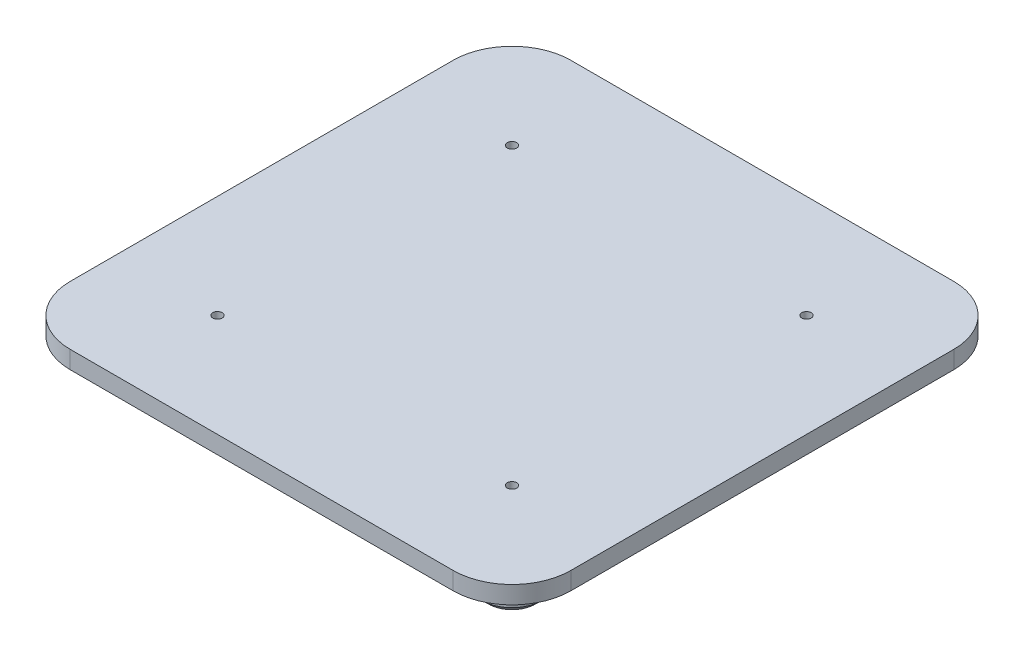
SolidWorks part; units mm, degrees
material "ABS"
ref_plane "前视基准面" through (0, 0, 0) normal (0, 0, 1) x (1, 0, 0)
ref_plane "上视基准面" through (0, 0, 0) normal (0, 1, 0) x (1, 0, 0)
ref_plane "右视基准面" through (0, 0, 0) normal (1, 0, 0) x (0, 0, -1)
sketch "草图1" plane through (0, 0, 0) normal (0, 1, 0) x (1, 0, 0)
  line L0 (-33.45, 33.45) -> (-33.45, -33.45)
  line L1 (-37.45, 37.45) -> (37.45, 37.45)
  line L2 (-37.45, 37.45) -> (-37.45, -37.45)
  line L3 (-37.45, -37.45) -> (37.45, -37.45)
  line L4 (37.45, 37.45) -> (37.45, -37.45)
  line L5 (-37.45, 37.45) -> (37.45, -37.45) construction
  line L6 (-37.45, -37.45) -> (37.45, 37.45) construction
  line L7 (-33.45, -33.45) -> (33.45, -33.45)
  line L8 (33.45, 33.45) -> (33.45, -33.45)
  line L9 (-33.45, 33.45) -> (33.45, 33.45)
  point P0 (0, 0)
  dimension "D1" = 74.9
  dimension "D3" = 74.9
  dimension "D2" = 4
extrude "凸台-拉伸1" add sketch "草图1" along normal blind 5
sketch "草图2" plane through (0, 5, 0) normal (0, 1, 0) x (1, 0, 0)
  line L1 (-42.5, -42.5) -> (42.5, -42.5)
  line L2 (-42.5, -42.5) -> (-42.5, 42.5)
  line L3 (-42.5, 42.5) -> (42.5, 42.5)
  line L4 (42.5, -42.5) -> (42.5, 42.5)
  line L5 (-42.5, -42.5) -> (42.5, 42.5) construction
  line L6 (-42.5, 42.5) -> (42.5, -42.5) construction
  point P0 (0, 0)
  dimension "D1" = 85
  dimension "D2" = 85
extrude "凸台-拉伸2" add sketch "草图2" along normal blind 3
fillet "圆角2" radius 5 4 edges at (-37.45, 2.5, 37.45) (-37.45, 2.5, -37.45) (37.45, 2.5, -37.45) (37.45, 2.5, 37.45)
sketch "草图3" plane through (0, 0, -37.45) normal (0, 0, -1) x (-1, 0, 0)
  line L0 (-32.45, 0) -> (32.45, 0) construction
  line L1 (22.0629, -5) -> (-22.0629, -5)
  line L2 (22.0629, -5) -> (22.0629, 5)
  line L3 (22.0629, 5) -> (-22.0629, 5)
  line L4 (-22.0629, -5) -> (-22.0629, 5)
  line L5 (22.0629, -5) -> (-22.0629, 5) construction
  line L6 (22.0629, 5) -> (-22.0629, -5) construction
  line L7 (-32.45, 5) -> (32.45, 5) construction
  point P0 (0, 0)
extrude "切除-拉伸1" cut sketch "草图3" against normal mid plane 206
ref_axis "基准轴1" through (0, 0, 0) along (0, -1, 0)
pattern_circular "阵列(圆周)1" count 2 every 90 about axis through (0, 0, 0) along (0, -1, 0) of "切除-拉伸1"
fillet "圆角3" radius 2 4 edges at (-33.45, 2.5, 33.45) (33.45, 2.5, 33.45) (33.45, 2.5, -33.45) (-33.45, 2.5, -33.45)
fillet "圆角4" radius 2 8 edges at (-22.0629, 2.5, -37.45) (-37.45, 2.5, -22.0629) (37.45, 2.5, -22.0629) (22.0629, 2.5, -37.45) (-37.45, 2.5, 22.0629) (-22.0629, 2.5, 37.45) (37.45, 2.5, 22.0629) (22.0629, 2.5, 37.45)
fillet "圆角5" radius 2 12 edges at (-26.7565, 5, 33.45) (-32.8642, 5, 32.8642) (33.45, 5, 26.7565) (26.7565, 5, 33.45) (-33.45, 5, -26.7565) (-32.8642, 5, -32.8642) (33.45, 5, -26.7565) (32.8642, 5, -32.8642) (-33.45, 5, 26.7565) (32.8642, 5, 32.8642) (-26.7565, 5, -33.45) (26.7565, 5, -33.45)
chamfer "倒角1" distance 1 angle 45 24 edges at (-22.0629, 0, 34.45) (-22.6487, 0, 36.8642) (-28.2565, 0, 37.45) (-35.9855, 0, 35.9855) (-37.45, 0, 28.2565) (-36.8642, 0, 22.6487) (-36.8642, 0, -22.6487) (-22.0629, 0, -34.45) (-37.45, 0, -28.2565) (-22.6487, 0, -36.8642) (-35.9855, 0, -35.9855) (-28.2565, 0, -37.45) (36.8642, 0, -22.6487) (37.45, 0, -28.2565) (35.9855, 0, -35.9855) (22.0629, 0, -34.45) (28.2565, 0, -37.45) (22.6487, 0, -36.8642) (36.8642, 0, 22.6487) (37.45, 0, 28.2565) (35.9855, 0, 35.9855) (28.2565, 0, 37.45) (22.0629, 0, 34.45) (22.6487, 0, 36.8642)
sketch "草图5" plane through (0, 5, 0) normal (0, -1, 0) x (-1, 0, 0)
  line L1 (-25, 25) -> (25, 25) construction
  line L2 (-25, 25) -> (-25, -25) construction
  line L3 (-25, -25) -> (25, -25) construction
  line L4 (25, 25) -> (25, -25) construction
  line L5 (-25, 25) -> (25, -25) construction
  line L6 (-25, -25) -> (25, 25) construction
  circle A0 centre (-25, 25) radius 0.8
  circle A1 centre (25, 25) radius 0.8
  circle A2 centre (25, -25) radius 0.8
  circle A3 centre (-25, -25) radius 0.8
  point P0 (0, 0)
  dimension "D3" = 1.6
  dimension "D1" = 50
  dimension "D2" = 50
extrude "切除-拉伸2" cut sketch "草图5" against normal blind 10
fillet "圆角9" radius 10 4 edges at (42.5, 6.5, -42.5) (-42.5, 6.5, -42.5) (42.5, 6.5, 42.5) (-42.5, 6.5, 42.5)
